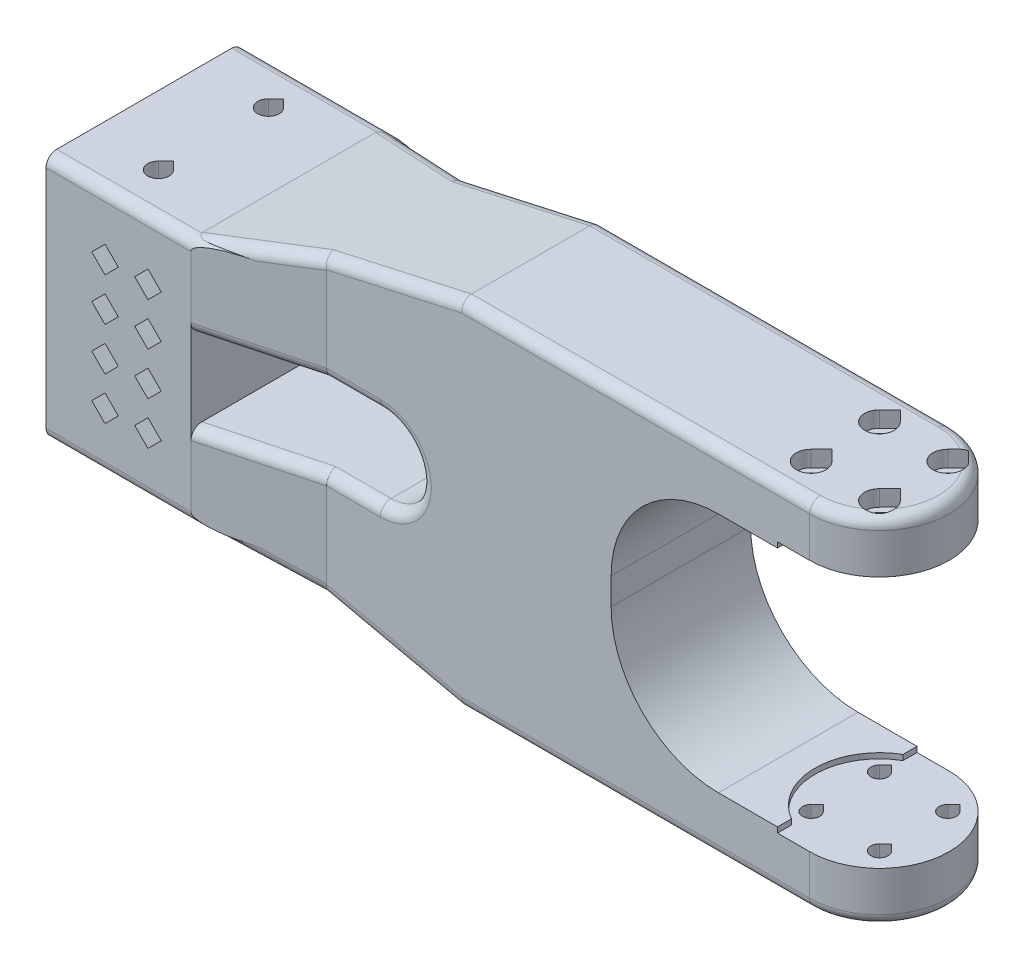
SolidWorks part; units mm, degrees
ref_plane "前视基准面" through (0, 0, 0) normal (0, 0, 1) x (1, 0, 0)
ref_plane "上视基准面" through (0, 0, 0) normal (0, 1, 0) x (1, 0, 0)
ref_plane "右视基准面" through (0, 0, 0) normal (1, 0, 0) x (0, 0, -1)
other "Configuration Table"
sketch "草图1" plane through (0, 0, 0) normal (0, 0, 1) x (1, 0, 0)
  line L0 (9.5, 15.3994) -> (-9.5, 15.3994)
  line L1 (9.5, 15.3994) -> (9.5, -16.4006)
  line L2 (9.5, -16.4006) -> (-9.5, -16.4006)
  line L4 (-9.5, 22.9994) -> (9.5, 22.9994)
  line L5 (-9.5, 22.9994) -> (-9.5, 15.3994)
  line L6 (-9.5, -23.0006) -> (9.5, -23.0006)
  line L7 (9.5, 15.3994) -> (9.5, -16.4006)
  line L8 (-9.5, -16.4006) -> (-9.5, -23.0006)
  line L9 (9.5, -23.0006) -> (17.5, -23.0006)
  line L10 (9.5, -16.4006) -> (9.5, 15.3994)
  line L11 (9.5, 22.9994) -> (17.5, 22.9994)
  line L12 (17.5, -23.0006) -> (17.5, 22.9994)
  dimension "D1" = 31.8
  dimension "D2" = 46
  dimension "D3" = 7.6
  dimension "D4" = 19
  dimension "D5" = 0
  dimension "D6" = 46
  dimension "D7" = 8
extrude "凸台-拉伸1" add sketch "草图1" along normal blind 24.6 contours L9 L12 L11 L4 L5 L0 L1 L2 L8 L6
sketch "草图2" plane through (0, -23.0006, 0) normal (0, -1, 0) x (1, 0, 0)
  line L0 (17.5, 24.6) -> (17.5, 0) construction
  line L1 (-9.5, 24.6) -> (17.5, 24.6)
  line L2 (-9.5, 24.6) -> (-9.5, 30.6)
  line L3 (-9.5, 30.6) -> (17.5, 30.6)
  line L4 (17.5, 24.6) -> (17.5, 30.6)
  line L5 (-9.5, 0) -> (17.5, 0)
  line L6 (-9.5, 0) -> (-9.5, -6)
  line L7 (-9.5, -6) -> (17.5, -6)
  line L8 (17.5, 0) -> (17.5, -6)
  dimension "D1" = 6
  dimension "D2" = 0
  dimension "D3" = 6
  dimension "D4" = 0
extrude "凸台-拉伸2" add sketch "草图2" against normal up to surface (46 mm away) up to face at (4, 22.9994, 12.3)
ref_plane "基准面1" through (0, 0, 24.6) normal (0, 0, -1) x (-1, 0, 0)
sketch "草图4" plane through (0, 0, 24.6) normal (0, 0, -1) x (-1, 0, 0)
  line L0 (-9.5, 15.3994) -> (9.5, 15.3994) construction
  line L1 (9.5, 15.3994) -> (-4.5, 15.3994)
  line L2 (9.5, 15.3994) -> (9.5, 17.2994)
  line L3 (9.5, 17.2994) -> (-4.5, 17.2994)
  line L4 (-4.5, 15.3994) -> (-4.5, 17.2994)
  line L5 (9.5, 22.9994) -> (9.5, -23.0006) construction
  line L6 (-9.5, -16.4006) -> (9.5, -16.4006)
  line L7 (-9.5, -16.4006) -> (-9.5, -17.6006)
  line L8 (-9.5, -17.6006) -> (9.5, -17.6006)
  line L9 (9.5, -16.4006) -> (9.5, -17.6006)
  dimension "D1" = 1.2
  dimension "D2" = 1.9
  dimension "D3" = 14
  dimension "D4" = 0
sketch "草图5" plane through (-9.5, 0, 0) normal (-1, 0, 0) x (0, 0, 1)
  line L0 (12.3, 15.3994) -> (12.3, -16.4006) construction
  line L1 (24.6, 15.3994) -> (0, 15.3994) construction
  line L2 (12.3, 16.5994) -> (12.3, 28.8634) construction
  line L4 (19.3, 15.3994) -> (5.3, 15.3994)
  line L5 (19.3, 15.3994) -> (19.3, 16.5994)
  line L6 (19.3, 16.5994) -> (5.3, 16.5994)
  line L8 (24.6, -16.4006) -> (0, -16.4006) construction
  line L9 (21.55, -16.4006) -> (3.05, -16.4006)
  line L10 (21.55, -16.4006) -> (21.55, -18.4006)
  line L11 (21.55, -18.4006) -> (3.05, -18.4006)
  line L13 (3.05, -16.4006) -> (3.05, -18.4006)
  line L14 (5.3, 15.3994) -> (5.3, 16.5994)
  line L15 (12.3, -18.4006) -> (12.3, -35.5702) construction
  dimension "D1" = 7
  dimension "D2" = 1.2
  dimension "D4" = 2
extrude "切除-拉伸1" cut sketch "草图5" against normal up to surface (19 mm away) up to face at (9.5, -0.5006, 12.3)
ref_plane "基准面2" through (140.5, 0, 0) normal (-1, 0, 0) x (0, 0, 1)
ref_plane "基准面3" through (0, -0.0006, 0) normal (0, -1, 0) x (-1, 0, 0)
ref_plane "基准面4" through (0, -33.0006, 0) normal (0, -1, 0) x (-1, 0, 0)
ref_plane "基准面5" through (0, 32.9994, 0) normal (0, -1, 0) x (-1, 0, 0)
ref_plane "基准面6" through (0, 0, 12.3) normal (0, 0, 1) x (1, 0, 0)
sketch "草图8" plane through (0, 0, 12.3) normal (0, 0, 1) x (1, 0, 0)
  line L0 (17.5, 22.9994) -> (62.5, 32.9994)
  line L1 (-21.196, 32.9994) -> (21.196, 32.9994) construction
  line L2 (62.5, 32.9994) -> (140.5, 32.9994)
  line L3 (140.5, 20.13) -> (140.5, -20.13) construction
  line L4 (17.5, 22.9994) -> (17.5, -23.0006) construction
  line L5 (-14.85, -0.0006) -> (14.85, -0.0006) construction
  line L6 (62.5, -33.0006) -> (140.5, -33.0006)
  line L7 (17.5, -23.0006) -> (62.5, -33.0006)
  line L8 (140.5, 32.9994) -> (140.5, 23.4994)
  line L9 (-9.5, -0.0006) -> (217.6979, -0.0006) construction
  line L10 (-9.5, 22.9994) -> (-9.5, -23.0006) construction
  line L11 (140.5, 23.4994) -> (90.5, 23.4994)
  line L12 (90.5, 23.4994) -> (90.5, -23.5006)
  line L13 (140.5, -33.0006) -> (140.5, -23.5006)
  line L14 (140.5, -23.5006) -> (90.5, -23.5006)
  line L15 (17.5, -23.0006) -> (62.5, -33.0006)
  line L16 (17.5, 22.9994) -> (17.5, -23.0006)
  point P24 (90.5, -0.0006)
  dimension "D1" = 0
  dimension "D2" = 45
  dimension "D3" = 9.5
  dimension "D4" = 50
extrude "凸台-拉伸3" add sketch "草图8" along normal mid plane 26 contours L16 L9 L12 L11 L8 L2 L0 | L9 L16 L7 L6 L13 L14 L12
sketch "草图9" plane through (0, 32.9994, 0) normal (0, 1, 0) x (1, 0, 0)
  line L0 (17.5, -12.3) -> (180.2833, -12.3) construction
  line L1 (17.5, -25.3) -> (17.5, 0.7) construction
  line L2 (-14.85, -12.3) -> (14.85, -12.3) construction
  line L3 (140.5, 20.13) -> (140.5, -20.13) construction
  line L4 (127.5, 0.7) -> (140.5, 0.7)
  line L5 (62.5, 0.7) -> (140.5, 0.7) construction
  line L6 (140.5, 0.7) -> (140.5, -25.3)
  line L7 (62.5, -25.3) -> (140.5, -25.3) construction
  line L8 (140.5, -25.3) -> (127.5, -25.3)
  arc A0 (127.5, -25.3) -> (127.5, 0.7) centre (127.5, -12.3) ccw
  line M2 (140.5, 0.7) -> (62.5, 0.7)
  line M4 (62.5, -25.3) -> (140.5, -25.3)
  line M5 (140.5, -25.3) -> (140.5, 0.7)
  dimension "D1" = 13
extrude "切除-拉伸2" cut sketch "草图9" against normal through all contours A0 L6 M2 | A0 M4 M5
sketch "草图10" plane through (0, 32.9994, 0) normal (0, 1, 0) x (1, 0, 0)
  line L0 (127.5, -12.3) -> (152.1511, 12.3511) construction
  line L1 (127.5, -12.3) -> (170.596, -12.3) construction
  line L2 (127.5, -12.3) -> (127.5, 15.5954) construction
  line L3 (133.864, -5.936) -> (133.864, 1.8241) construction
  line L4 (133.864, -2.047) -> (131.9194, -3.9915)
  line L5 (133.864, -2.047) -> (135.8085, -3.9915)
  line L6 (133.864, -14.7749) -> (131.9194, -16.7194)
  line L7 (133.864, -14.7749) -> (135.8085, -16.7194)
  line L8 (121.136, -14.7749) -> (119.1915, -16.7194)
  line L9 (121.136, -14.7749) -> (123.0806, -16.7194)
  line L10 (121.136, -2.047) -> (119.1915, -3.9915)
  line L11 (121.136, -2.047) -> (123.0806, -3.9915)
  circle A0 centre (127.5, -12.3) radius 9 construction
  arc A1 (131.9194, -3.9915) -> (135.8085, -3.9915) centre (133.864, -5.936) ccw
  arc A2 (131.9194, -16.7194) -> (135.8085, -16.7194) centre (133.864, -18.664) ccw
  arc A3 (119.1915, -16.7194) -> (123.0806, -16.7194) centre (121.136, -18.664) ccw
  arc A4 (119.1915, -3.9915) -> (123.0806, -3.9915) centre (121.136, -5.936) ccw
  point P3 (133.864, -5.936)
  point P6 (133.864, -18.664)
  point P7 (121.136, -18.664)
  point P9 (121.136, -5.936)
  dimension "D1" = 18
  dimension "D3" = 5.5
  dimension "D2" = 45
extrude "切除-拉伸3" cut sketch "草图10" against normal blind 3
sketch "草图11" plane through (0, 32.9994, 0) normal (0, 1, 0) x (1, 0, 0)
  line L0 (121.136, -5.936) -> (121.136, -2.047) construction
  line L1 (121.136, -3.6733) -> (120.0047, -4.8047)
  line L2 (121.136, -3.6733) -> (122.2674, -4.8047)
  line L3 (133.864, -3.6733) -> (132.7326, -4.8047)
  line L4 (133.864, -3.6733) -> (134.9953, -4.8047)
  line L5 (133.864, -16.4012) -> (132.7326, -17.5326)
  line L6 (133.864, -16.4012) -> (134.9953, -17.5326)
  line L7 (121.136, -16.4012) -> (120.0047, -17.5326)
  line L8 (121.136, -16.4012) -> (122.2674, -17.5326)
  circle A0 centre (127.5, -12.3) radius 9 construction
  arc A1 (120.0047, -4.8047) -> (122.2674, -4.8047) centre (121.136, -5.936) ccw
  arc A5 (132.7326, -4.8047) -> (134.9953, -4.8047) centre (133.864, -5.936) ccw
  arc A6 (132.7326, -17.5326) -> (134.9953, -17.5326) centre (133.864, -18.664) ccw
  arc A7 (120.0047, -17.5326) -> (122.2674, -17.5326) centre (121.136, -18.664) ccw
  point P6 (121.136, -18.664)
  point P7 (133.864, -18.664)
  point P9 (133.864, -5.936)
  dimension "D1" = 3.2
  dimension "D2" = 90
extrude "切除-拉伸4" cut sketch "草图11" against normal through all
sketch "草图13" plane through (0, -33.0006, 0) normal (0, -1, 0) x (1, 0, 0)
  line L0 (121.136, 18.664) -> (121.136, 11.9587) construction
  line L1 (121.136, 14.7749) -> (119.1915, 16.7194)
  line L2 (121.136, 14.7749) -> (123.0806, 16.7194)
  line L3 (133.864, 14.7749) -> (131.9194, 16.7194)
  line L4 (133.864, 14.7749) -> (135.8085, 16.7194)
  line L5 (133.864, 2.047) -> (131.9194, 3.9915)
  line L6 (133.864, 2.047) -> (135.8085, 3.9915)
  line L7 (121.136, 2.047) -> (119.1915, 3.9915)
  line L8 (121.136, 2.047) -> (123.0806, 3.9915)
  arc A0 (123.0806, 16.7194) -> (119.1915, 16.7194) centre (121.136, 18.664) ccw
  arc A1 (135.8085, 16.7194) -> (131.9194, 16.7194) centre (133.864, 18.664) ccw
  arc A2 (135.8085, 3.9915) -> (131.9194, 3.9915) centre (133.864, 5.936) ccw
  arc A3 (123.0806, 3.9915) -> (119.1915, 3.9915) centre (121.136, 5.936) ccw
  point P3 (133.864, 18.664)
  point P4 (133.864, 5.936)
  point P6 (121.136, 5.936)
  dimension "D1" = 5.5
  dimension "D2" = 90
  dimension "D3" = 90
  dimension "D4" = 90
  dimension "D5" = 90
extrude "切除-拉伸5" cut sketch "草图13" against normal blind 3
sketch "草图15" plane through (0, 23.4994, 0) normal (0, -1, 0) x (1, 0, 0)
  line L0 (127.5, 25.3) -> (90.5, 25.3)
  line L1 (90.5, 25.3) -> (90.5, -0.7)
  line L2 (90.5, -0.7) -> (127.5, -0.7)
  arc A0 (127.5, -0.7) -> (127.5, 25.3) centre (127.5, 12.3) ccw
extrude "凸台-拉伸4" add sketch "草图15" along normal mid plane 2
mirror "镜向1" about plane through (0, -0.0006, 0) normal (0, -1, 0) of "凸台-拉伸4"
sketch "草图16" plane through (0, -33.0006, 0) normal (0, -1, 0) x (1, 0, 0)
  line L0 (121.136, 16.4012) -> (120.0047, 17.5326)
  line L1 (121.136, 16.4012) -> (122.2674, 17.5326)
  line L2 (133.864, 16.4012) -> (132.7326, 17.5326)
  line L3 (133.864, 16.4012) -> (134.9953, 17.5326)
  line L4 (133.864, 3.6733) -> (132.7326, 4.8047)
  line L5 (133.864, 3.6733) -> (134.9953, 4.8047)
  line L6 (121.136, 3.6733) -> (122.2674, 4.8047)
  line L7 (121.136, 3.6733) -> (120.0047, 4.8047)
  arc A0 (122.2674, 17.5326) -> (120.0047, 17.5326) centre (121.136, 18.664) ccw
  arc A1 (134.9953, 17.5326) -> (132.7326, 17.5326) centre (133.864, 18.664) ccw
  arc A2 (134.9953, 4.8047) -> (132.7326, 4.8047) centre (133.864, 5.936) ccw
  arc A3 (122.2674, 4.8047) -> (120.0047, 4.8047) centre (121.136, 5.936) ccw
extrude "切除-拉伸6" cut sketch "草图16" against normal through all contours A0 L0 L1 | A1 L2 L3 | A2 L4 L5 | A3 L7 L6
fillet "圆角2" radius 20 2 edges at (90.5, 22.4994, 12.3) (90.5, -22.5006, 12.3)
sketch "草图17" plane through (0, -22.5006, 0) normal (0, 1, 0) x (1, 0, 0)
  line L2 (121.5, 0.7) -> (121.5, -1.9077)
  line L3 (127.5, 0.7) -> (121.5, 0.7)
  line L6 (127.5, -25.3) -> (121.5, -25.3)
  line L9 (121.5, -22.6923) -> (121.5, -25.3)
  arc A2 (127.5, -25.3) -> (127.5, 0.7) centre (127.5, -12.3) ccw
  arc A3 (121.5, -1.9077) -> (121.5, -22.6923) centre (127.5, -12.3) ccw
  dimension "D1" = 24
  dimension "D2" = 6
extrude "切除-拉伸7" cut sketch "草图17" against normal blind 2
mirror "镜向2" about plane through (0, -0.0006, 0) normal (0, -1, 0) of "切除-拉伸7"
sketch "草图18" plane through (0, -0.0006, 0) normal (0, -1, 0) x (-1, 0, 0)
  line L0 (-17.5, 6) -> (-37.5, 0.7)
  line L1 (-17.5, 0.7) -> (-62.5, 0.7) construction
  line L2 (-37.5, 0.7) -> (-17.5, 0.7)
  line L3 (-17.5, 0.7) -> (-17.5, 6)
  dimension "D1" = 20
extrude "凸台-拉伸5" add sketch "草图18" along normal up to surface and the other way up to surface up to face at (40, -28.0006, 12.3) other way up to face at (40, 27.9994, 12.3)
mirror "镜向3" about plane through (0, 0, 12.3) normal (0, 0, 1) of "凸台-拉伸5"
sketch "草图19" plane through (0, 0, 30.6) normal (0, 0, 1) x (1, 0, 0)
  line L0 (17.5, 7.4994) -> (17.5, -7.5006)
  line L1 (17.5, 22.9994) -> (17.5, -23.0006) construction
  line L2 (-14.85, -0.0006) -> (14.85, -0.0006) construction
  line L3 (47.5, 7.4994) -> (17.5, 7.4994)
  line L4 (47.5, -7.5006) -> (17.5, -7.5006)
  arc A0 (47.5, -7.5006) -> (47.5, 7.4994) centre (47.5, -0.0006) ccw
  dimension "D2" = 15
extrude "切除-拉伸10" cut sketch "草图19" against normal through all
fillet "圆角3" radius 2 26 edges at (140.5, 32.9994, 12.3) (140.5, -33.0006, 12.3) (134.8362, 32.9994, 3.0192) (134.8362, -33.0006, 3.0192) (50, 30.2216, -0.7) (50, -30.2229, -0.7) (27.5, -25.2229, -3.35) (27.5, 25.2216, -3.35) (50, 30.2216, 25.3) (50, -30.2229, 25.3) (27.5, -25.2229, 27.95) (27.5, 25.2216, 27.95) (27.5, 7.4994, 27.95) (27.5, -7.5006, 27.95) (55, -0.0006, 25.3) (55, -0.0006, -0.7) (27.5, -7.5006, -3.35) (42.5, -7.5006, -0.7) (42.5, -7.5006, 25.3) (42.5, 7.4994, -0.7) (27.5, 7.4994, -3.35) (42.5, 7.4994, 25.3) (95, -33.0006, -0.7) (95, 32.9994, 25.3) (95, -33.0006, 25.3) (95, 32.9994, -0.7)
fillet "圆角4" radius 2 4 edges at (4, -23.0006, -6) (4, 22.9994, -6) (4, 22.9994, 30.6) (4, -23.0006, 30.6)
ref_plane "基准面7" through (9.5, 0, 0) normal (-1, 0, 0) x (0, 0, 1)
sketch "草图20" plane through (0, 0, 30.6) normal (0, 0, 1) x (1, 0, 0)
  line L0 (4.5, 15.3994) -> (16.5223, 15.3994) construction
  line L1 (9.5, 14.1728) -> (7.0251, 11.698)
  line L2 (9.5, 35.215) -> (9.5, -35.215) construction
  line L3 (7.0251, 11.698) -> (9.5, 9.2231)
  line L5 (11.9749, 11.698) -> (9.5, 9.2231)
  line L6 (9.5, 14.1728) -> (11.9749, 11.698)
  line L7 (9.5, 14.1728) -> (9.5, 6.0275) construction
  line L8 (7.0251, 3.698) -> (9.5, 1.2231)
  line L9 (11.9749, 3.698) -> (9.5, 1.2231)
  line L10 (9.5, 6.1728) -> (11.9749, 3.698)
  line L11 (9.5, 6.1728) -> (7.0251, 3.698)
  line L12 (7.0251, -4.302) -> (9.5, -6.7769)
  line L13 (11.9749, -4.302) -> (9.5, -6.7769)
  line L14 (9.5, -1.8272) -> (11.9749, -4.302)
  line L15 (9.5, -1.8272) -> (7.0251, -4.302)
  line L16 (7.0251, -12.302) -> (9.5, -14.7769)
  line L17 (11.9749, -12.302) -> (9.5, -14.7769)
  line L18 (9.5, -9.8272) -> (11.9749, -12.302)
  line L19 (9.5, -9.8272) -> (7.0251, -12.302)
  line L20 (-0.9749, 11.698) -> (1.5, 9.2231)
  line L21 (3.9749, 11.698) -> (1.5, 9.2231)
  line L22 (1.5, 14.1728) -> (3.9749, 11.698)
  line L23 (1.5, 14.1728) -> (-0.9749, 11.698)
  line L24 (-0.9749, 3.698) -> (1.5, 1.2231)
  line L25 (3.9749, 3.698) -> (1.5, 1.2231)
  line L26 (1.5, 6.1728) -> (3.9749, 3.698)
  line L27 (1.5, 6.1728) -> (-0.9749, 3.698)
  line L28 (-0.9749, -4.302) -> (1.5, -6.7769)
  line L29 (3.9749, -4.302) -> (1.5, -6.7769)
  line L30 (1.5, -1.8272) -> (3.9749, -4.302)
  line L31 (1.5, -1.8272) -> (-0.9749, -4.302)
  line L32 (-0.9749, -12.302) -> (1.5, -14.7769)
  line L33 (3.9749, -12.302) -> (1.5, -14.7769)
  line L34 (1.5, -9.8272) -> (3.9749, -12.302)
  line L35 (1.5, -9.8272) -> (-0.9749, -12.302)
  dimension "D1" = 4
  dimension "D2" = 3.5
  dimension "D3" = 2
extrude "切除-拉伸11" cut sketch "草图20" against normal through all
sketch "草图28" plane through (0, 24.4994, 0) normal (0, -1, 0) x (1, 0, 0)
  line L0 (127.5, 25.3) -> (121.5, 25.3)
  line L1 (121.5, 25.3) -> (121.5, 22.6923)
  line L2 (127.5, -0.7) -> (121.5, -0.7)
  line L3 (121.5, -0.7) -> (121.5, 1.9077)
  arc A0 (127.5, -0.7) -> (127.5, 25.3) centre (127.5, 12.3) ccw
  arc A2 (121.5, 22.6923) -> (121.5, 1.9077) centre (127.5, 12.3) ccw
extrude "凸台-拉伸6" add sketch "草图28" along normal blind 1
mirror "镜向4" about plane through (0, -0.0006, 0) normal (0, -1, 0) of "凸台-拉伸6"
sketch "草图30" plane through (0, 32.9994, 0) normal (0, 1, 0) x (1, 0, 0)
  line L0 (121.136, -3.6733) -> (120.0047, -4.8047)
  line L1 (121.136, -3.6733) -> (122.2674, -4.8047)
  line L2 (133.864, -3.6733) -> (132.7326, -4.8047)
  line L3 (133.864, -3.6733) -> (134.9953, -4.8047)
  line L4 (133.864, -16.4012) -> (132.7326, -17.5326)
  line L5 (133.864, -16.4012) -> (134.9953, -17.5326)
  line L6 (121.136, -16.4012) -> (120.0047, -17.5326)
  line L7 (121.136, -16.4012) -> (122.2674, -17.5326)
  arc A0 (120.0047, -4.8047) -> (122.2674, -4.8047) centre (121.136, -5.936) ccw
  arc A1 (132.7326, -4.8047) -> (134.9953, -4.8047) centre (133.864, -5.936) ccw
  arc A2 (132.7326, -17.5326) -> (134.9953, -17.5326) centre (133.864, -18.664) ccw
  arc A3 (120.0047, -17.5326) -> (122.2674, -17.5326) centre (121.136, -18.664) ccw
  point P1 (133.864, -3.6733)
  point P8 (133.864, -16.4012)
  point P10 (121.136, -16.4012)
extrude "切除-拉伸16" cut sketch "草图30" against normal through all
ref_plane "基准面8" through (0, 0, 0) normal (0, 0, 1) x (1, 0, 0)
sketch "草图31" plane through (0, 22.9994, 0) normal (0, 1, 0) x (1, 0, 0)
  line L0 (9.5, 35.215) -> (9.5, -35.215) construction
  line L1 (32.6208, -24.6) -> (-32.6208, -24.6) construction
  line L2 (3.3, -22.45) -> (3.3, -14.9163) construction
  line L3 (3.3, -21.0358) -> (2.5929, -21.7429)
  line L4 (3.3, -21.0358) -> (4.0071, -21.7429)
  line L5 (-29.0746, 0) -> (29.0746, 0) construction
  line L6 (3.5, -2.15) -> (3.5, 5.3837) construction
  line L7 (3.5, -0.7358) -> (2.7929, -1.4429)
  line L8 (3.5, -0.7358) -> (4.2071, -1.4429)
  arc A0 (2.5929, -21.7429) -> (4.0071, -21.7429) centre (3.3, -22.45) ccw
  arc A1 (2.7929, -1.4429) -> (4.2071, -1.4429) centre (3.5, -2.15) ccw
  point P1 (3.5, -2.15)
  point P13 (3.3, -22.45)
  point P18 (3.5, -2.15)
  dimension "D3" = 2
  dimension "D7" = 2
  dimension "D1" = 6.2
  dimension "D2" = 2.15
  dimension "D4" = 90
  dimension "D5" = 2.15
  dimension "D6" = 6
  dimension "D8" = 90
extrude "切除-拉伸17" cut sketch "草图31" against normal up to surface (7.6 mm away) up to face at (0, 15.3994, 2.65)
sketch "草图32" plane through (0, 22.9994, 0) normal (0, 1, 0) x (1, 0, 0)
  line L0 (3.3, -22.45) -> (3.3, -15.3092) construction
  line L1 (3.3, -19.6216) -> (1.8858, -21.0358)
  line L2 (3.3, -19.6216) -> (4.7142, -21.0358)
  line L3 (3.5, -2.15) -> (3.5, 4.9908) construction
  line L4 (3.5, 0.6784) -> (2.0858, -0.7358)
  line L5 (3.5, 0.6784) -> (4.9142, -0.7358)
  arc A0 (1.8858, -21.0358) -> (4.7142, -21.0358) centre (3.3, -22.45) ccw
  arc A1 (2.0858, -0.7358) -> (4.9142, -0.7358) centre (3.5, -2.15) ccw
  point P1 (3.5, -2.15)
  point P9 (3.3, -22.45)
  point P14 (3.5, -2.15)
  dimension "D1" = 4
  dimension "D3" = 4
  dimension "D2" = 90
  dimension "D4" = 90
extrude "切除-拉伸18" cut sketch "草图32" against normal blind 3
sketch "草图34" plane through (0, -23.0006, 0) normal (0, -1, 0) x (1, 0, 0)
  line L0 (9.5, 35.215) -> (9.5, -35.215) construction
  line L1 (-32.6208, 24.6) -> (32.6208, 24.6) construction
  line L2 (7.1, 22.45) -> (7.1, 17.1922) construction
  line L3 (7.1, 21.0358) -> (7.8071, 21.7429)
  line L4 (7.1, 21.0358) -> (6.3929, 21.7429)
  line L5 (29.0746, 0) -> (-29.0746, 0) construction
  line L6 (7.1, 2.15) -> (7.1, -3.1078) construction
  line L7 (7.1, 0.7358) -> (7.8071, 1.4429)
  line L8 (7.1, 0.7358) -> (6.3929, 1.4429)
  arc A0 (7.8071, 21.7429) -> (6.3929, 21.7429) centre (7.1, 22.45) ccw
  arc A1 (7.8071, 1.4429) -> (6.3929, 1.4429) centre (7.1, 2.15) ccw
  point P1 (7.1, 2.15)
  point P8 (7.1, 22.45)
  point P16 (7.1, 2.15)
  dimension "D3" = 2
  dimension "D7" = 2
  dimension "D1" = 2.4
  dimension "D2" = 2.15
  dimension "D4" = 90
  dimension "D5" = 2.4
  dimension "D6" = 2.15
  dimension "D8" = 90
extrude "切除-拉伸19" cut sketch "草图34" against normal up to surface (6.6 mm away) up to face at (0, -16.4006, 23.075)
sketch "草图35" plane through (0, -23.0006, 0) normal (0, -1, 0) x (1, 0, 0)
  line L0 (7.1, 22.45) -> (7.1, 15.0614) construction
  line L1 (7.1, 19.6216) -> (5.6858, 21.0358)
  line L2 (7.1, 19.6216) -> (8.5142, 21.0358)
  line L3 (7.1, 2.15) -> (7.1, -5.2386) construction
  line L4 (7.1, -0.6784) -> (5.6858, 0.7358)
  line L5 (7.1, -0.6784) -> (8.5142, 0.7358)
  arc A0 (8.5142, 21.0358) -> (5.6858, 21.0358) centre (7.1, 22.45) ccw
  arc A1 (8.5142, 0.7358) -> (5.6858, 0.7358) centre (7.1, 2.15) ccw
  point P3 (7.1, 2.15)
  point P6 (7.1, 22.45)
  point P11 (7.1, 2.15)
  dimension "D1" = 4
  dimension "D3" = 4
  dimension "D2" = 90
  dimension "D4" = 90
extrude "切除-拉伸20" cut sketch "草图35" against normal blind 3
sketch "草图37" plane through (-9.5, 0, 0) normal (-1, 0, 0) x (0, 0, 1)
  line L0 (0, -29.0746) -> (0, 29.0746) construction
  line L1 (0, -16.4006) -> (3.05, -16.4006)
  line L2 (0, -16.4006) -> (0, -16.5506)
  line L3 (0, -16.5506) -> (3.05, -16.5506)
  line L4 (3.05, -16.4006) -> (3.05, -16.5506)
  line L5 (3.05, -16.4006) -> (0, -16.4006) construction
  line L6 (3.05, -16.4006) -> (3.05, -18.4006) construction
  line L7 (24.6, 32.6208) -> (24.6, -32.6208) construction
  line L8 (24.6, -16.4006) -> (21.55, -16.4006)
  line L9 (24.6, -16.4006) -> (24.6, -16.6006)
  line L10 (24.6, -16.6006) -> (21.55, -16.6006)
  line L11 (21.55, -16.4006) -> (21.55, -16.6006)
  line L12 (24.6, -16.4006) -> (21.55, -16.4006) construction
  line L13 (21.55, -18.4006) -> (21.55, -16.4006) construction
  dimension "D1" = 0.2
  dimension "D2" = 0.15
extrude "切除-拉伸21" cut sketch "草图37" against normal up to surface (19 mm away) up to face at (9.5, -16.4947, 12.3)
